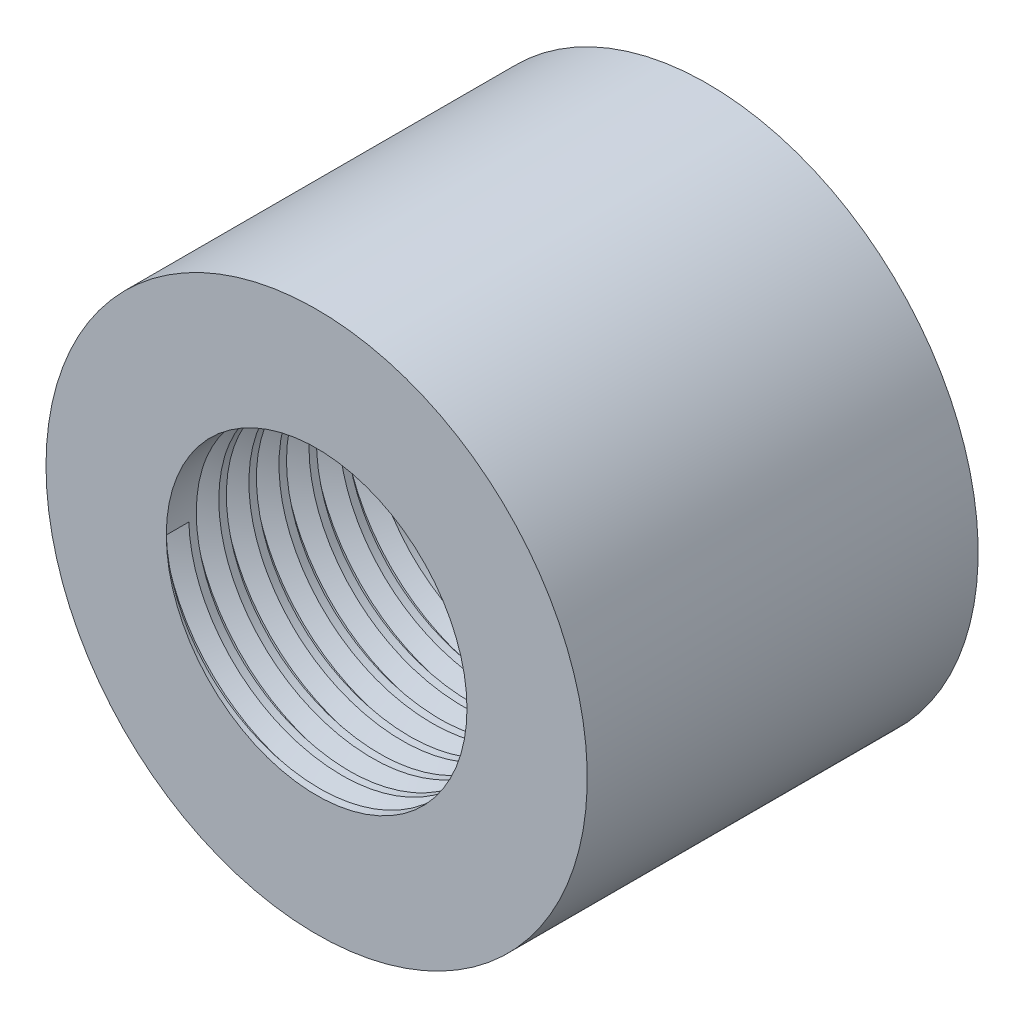
SolidWorks part; units mm, degrees
ref_plane "Front Plane" through (0, 0, 0) normal (0, 0, 1) x (1, 0, 0)
ref_plane "Top Plane" through (0, 0, 0) normal (0, 1, 0) x (1, 0, 0)
ref_plane "Right Plane" through (0, 0, 0) normal (1, 0, 0) x (0, 0, -1)
sketch "Sketch1" plane through (0, 0, 0) normal (0, 0, 1) x (1, 0, 0)
  circle A0 centre (0, 0) radius 9
  circle A1 centre (0, 0) radius 5
  dimension "D1" = 10
  dimension "D2" = 4
extrude "Boss-Extrude1" add sketch "Sketch1" along normal blind 13
sketch "Sketch4" plane through (0, 0, 0) normal (0, 0, -1) x (-1, 0, 0)
  circle A0 centre (0, 0) radius 7
  dimension "D1" = 14
extrude "Cut-Extrude1" cut sketch "Sketch4" against normal blind 3
thread "Thread1" start angle 0, offset 0, length 0, pitch 1, diameter 10
ref_plane "Plane2" through (-5, 0, 13) normal (0, -1, 0) x (-1, 0, 0)
sketch "Thread Profile2" plane through (-5, 0, 13) normal (0, -1, 0) x (-1, 0, 0)
  line L0 (0, 0) -> (0, 1) construction
  line L1 (0, 0) -> (0.5413, 0.3125)
  line L2 (0.5413, 0.3125) -> (0.5413, 0.4375)
  line L3 (0.5413, 0.4375) -> (0, 0.75)
  line L4 (0.5413, 0.375) -> (0, 0.375) construction
  line L11 (0, 0) -> (0, 0.75)
  point P2 (0, 0)
  dimension "Pitch" = 1
  dimension "Profile_Angle" = 60
  dimension "Profile_Land" = 0.125
  dimension "Profile_Height" = 0.5413
